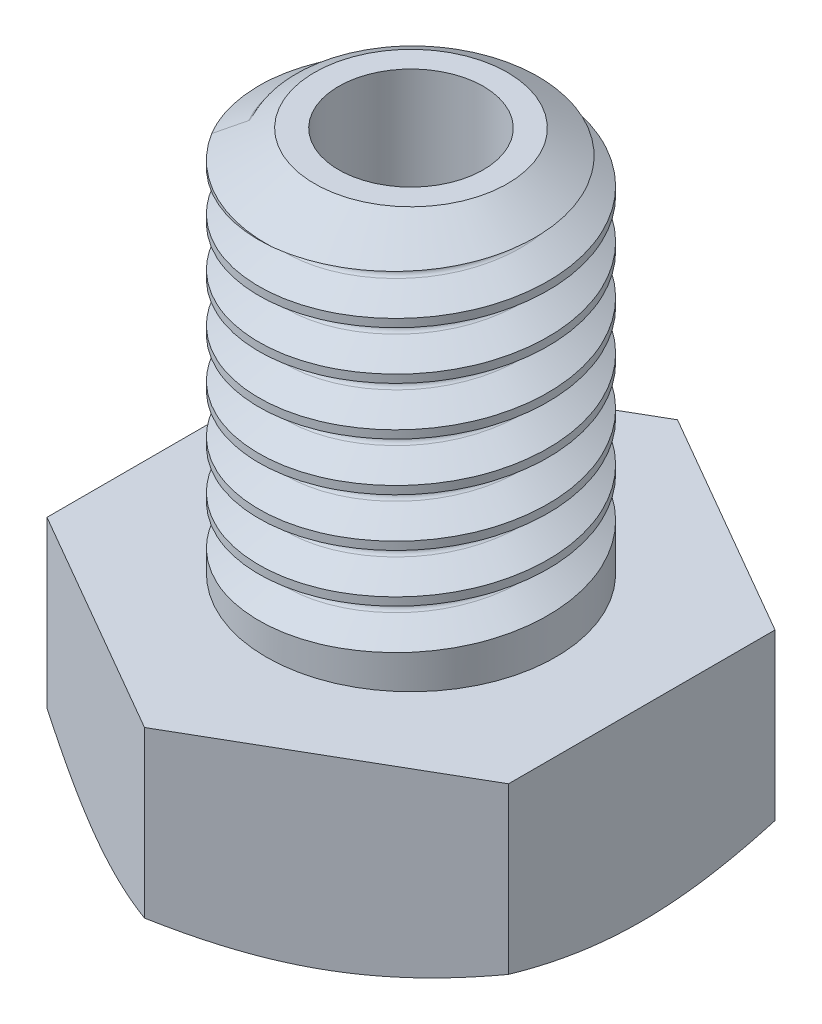
SolidWorks part; units mm, degrees
ref_plane "Front Plane" through (0, 0, 0) normal (0, 0, 1) x (1, 0, 0)
ref_plane "Top Plane" through (0, 0, 0) normal (0, 1, 0) x (1, 0, 0)
ref_plane "Right Plane" through (0, 0, 0) normal (1, 0, 0) x (0, 0, -1)
sketch "Sketch1" plane through (0, 0, 0) normal (0, 1, 0) x (1, 0, 0)
  line L0 (0, 0) -> (7, 0) construction
  line L1 (4.7848, -2.7625) -> (4.7848, 2.7625)
  line L2 (4.7848, 2.7625) -> (0, 5.525)
  line L3 (0, 5.525) -> (-4.7848, 2.7625)
  line L4 (-4.7848, 2.7625) -> (-4.7848, -2.7625)
  line L5 (-4.7848, -2.7625) -> (0, -5.525)
  line L6 (0, -5.525) -> (4.7848, -2.7625)
  line L7 (0, 0) -> (4.7848, 2.7625) construction
  circle A0 centre (0, 0) radius 5.525 construction
  dimension "D1" = 11.05
  dimension "D2" = 7
  dimension "D3" = 30
extrude "Boss-Extrude1" add sketch "Sketch1" along normal blind 4
sketch "Sketch2" plane through (0, 4, 0) normal (0, 1, 0) x (1, 0, 0)
  circle A0 centre (0, 0) radius 3
  dimension "D1" = 6
extrude "Boss-Extrude2" add sketch "Sketch2" along normal blind 8
ref_plane "Plane1" through (0, 13, 0) normal (0, 1, 0) x (1, 0, 0)
sketch "Sketch3" plane through (0, 13, 0) normal (0, 1, 0) x (1, 0, 0)
  circle A0 centre (0, 0) radius 2.675
  dimension "D1" = 5.35
curve "Helix/Spiral1" pitch 1 height 8.5 radius 2.675 centre (0, 13, 0) axis (0, -1, 0) start towards (0, 0, 1)
sketch "Sketch4" plane through (0, 0, 0) normal (1, 0, 0) x (0, 0, -1)
  line L0 (0, 0) -> (0, 13) construction
  line L1 (0, 13) -> (-2.3865, 13) construction
  line L2 (0, 13) -> (0, 14) construction
  line L3 (0, 14) -> (-3, 14) construction
  line L4 (-3, 14) -> (-3, 12.5) construction
  line L5 (-2.3865, 13.0625) -> (-2.3865, 12.9375) construction
  line L6 (-2.3865, 13) -> (-3.3865, 13) construction
  line L7 (-2.3865, 13.0625) -> (-3.2525, 13.5625) construction
  line L8 (-2.3865, 12.9375) -> (-3.2525, 12.4375) construction
  line L9 (-2.4406, 13.0938) -> (-3, 13.4167)
  line L10 (-3, 13.4167) -> (-3, 12.5833)
  line L11 (-3, 12.5833) -> (-2.4406, 12.9062)
  arc A0 (-2.4406, 12.9062) -> (-2.4406, 13.0938) centre (-2.4948, 13) ccw
  point P9 (-3, 13.4167)
  point P15 (-3, 12.5833)
  dimension "D1" = 13
  dimension "D2" = 2.3865
  dimension "D3" = 1
  dimension "D4" = 3
  dimension "D5" = 1.5
  dimension "D6" = 0.0625
  dimension "D7" = 0.125
  dimension "D8" = 1
  dimension "D9" = 1
  dimension "D10" = 1
  dimension "D11" = 30
  dimension "D12" = 60
sweep "Cut-Sweep1" cut profiles "Sketch4" path "Helix/Spiral1" align with end faces yes
sketch "Sketch5" plane through (0, 0, 0) normal (1, 0, 0) x (0, 0, -1)
  line L0 (0, 0) -> (0, 12) construction
  line L1 (0, 12) -> (3, 12) construction
  line L2 (3, 12) -> (3, 4.5) construction
  line L3 (3, 4.5) -> (0, 4.5) construction
  line L4 (3, 12) -> (2, 12)
  line L5 (2, 12) -> (3, 11.4226)
  line L6 (3, 11.4226) -> (3, 12)
  line L7 (0, 0) -> (5.525, 0) construction
  line L8 (5.525, 0) -> (4.525, 0)
  line L9 (4.525, 0) -> (5.525, 0.5774)
  line L10 (5.525, 4) -> (5.525, 0) construction
  line L11 (5.525, 0.5774) -> (5.525, 0)
  dimension "D1" = 12
  dimension "D2" = 3
  dimension "D3" = 7.5
  dimension "D4" = 3
  dimension "D5" = 1
  dimension "D6" = 30
  dimension "D7" = 1
  dimension "D8" = 30
revolve "Cut-Revolve1" cut sketch "Sketch5" angle 360 about L0
sketch "Sketch6" plane through (0, 0, 0) normal (1, 0, 0) x (0, 0, -1)
  line L0 (0, 0) -> (0, 12)
  line L1 (2, 12) -> (-2, 12) construction
  line L2 (0, 12) -> (1.5, 12)
  line L3 (1.5, 12) -> (1.5, 2)
  line L4 (1.5, 2) -> (2.5, 0)
  line L5 (-4.525, 0) -> (4.525, 0) construction
  line L6 (2.5, 0) -> (0, 0)
  dimension "D1" = 2.5
  dimension "D2" = 1.5
  dimension "D3" = 2
revolve "Cut-Revolve2" cut sketch "Sketch6" angle 360 about L0
